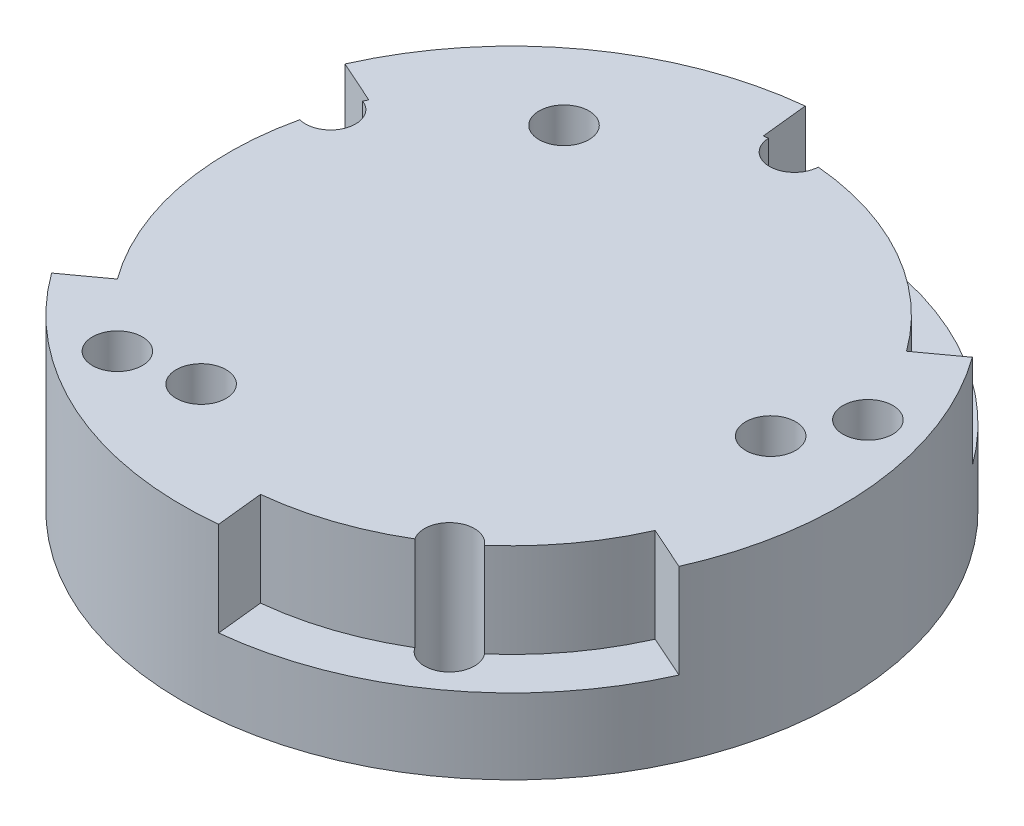
SolidWorks part; units mm, degrees
ref_plane "Front Plane" through (0, 0, 0) normal (0, 0, 1) x (1, 0, 0)
ref_plane "Top Plane" through (0, 0, 0) normal (0, 1, 0) x (1, 0, 0)
ref_plane "Right Plane" through (0, 0, 0) normal (1, 0, 0) x (0, 0, -1)
sketch "Sketch2" plane through (0, 0, 0) normal (0, 1, 0) x (1, 0, 0)
  circle A8 centre (0, 0) radius 35
  dimension "D1" = 70
extrude "Boss-Extrude1" add sketch "Sketch2" along normal blind 8
sketch "Sketch4" plane through (0, 8, 0) normal (0, 1, 0) x (1, 0, 0)
  circle A0 centre (0, 0) radius 30 construction
  circle A1 centre (0, 30) radius 2.65
  circle A2 centre (28.5317, 9.2705) radius 2.65
  circle A3 centre (17.6336, -24.2705) radius 2.65
  circle A4 centre (-17.6336, -24.2705) radius 2.65
  circle A5 centre (-28.5317, 9.2705) radius 2.65
  point P16 (0, 0)
  dimension "D1" = 5.3
  dimension "D2" = 30
  dimension "D4" = 30
  dimension "D5" = 30
  dimension "D3" = 5
extrude "Cut-Extrude1" cut sketch "Sketch4" against normal blind 8 from surface starting at face at (0, 8, 35)
sketch "Sketch5" plane through (0, 8, 0) normal (0, 1, 0) x (1, 0, 0)
  line L2 (0, 0) -> (-3.6585, 34.8083) construction
  line L3 (0, 0) -> (-31.9741, 14.2358) construction
  line L4 (-31.9741, 14.2358) -> (-27.4064, 12.2021)
  line L5 (0, 0) -> (-50000, 0) construction
  line L6 (28.3156, 20.5725) -> (24.2705, 17.6336)
  line L7 (-3.6585, 34.8083) -> (-3.1359, 29.8357)
  line L8 (31.9741, -14.2358) -> (27.4064, -12.2021)
  line L9 (3.6585, -34.8083) -> (3.1359, -29.8357)
  line L10 (-20.5725, 28.3156) -> (0, 0) construction
  line L11 (34.8083, 3.6585) -> (0, 0) construction
  line L12 (-14.2358, -31.9741) -> (0, 0) construction
  line L13 (-28.3156, -20.5725) -> (-24.2705, -17.6336)
  arc A2 (-3.6585, 34.8083) -> (-31.9741, 14.2358) centre (0, 0) ccw
  circle A3 centre (0, 0) radius 35 construction
  arc A4 (31.9741, -14.2358) -> (28.3156, 20.5725) centre (0, 0) ccw
  arc A5 (-28.3156, -20.5725) -> (3.6585, -34.8083) centre (0, 0) ccw
  circle A6 centre (0, 0) radius 25 construction
  circle A7 centre (-14.6946, 20.2254) radius 2.65
  circle A9 centre (24.863, 2.6132) radius 2.65
  circle A10 centre (0, 0) radius 30
  circle A11 centre (-10.1684, -22.8386) radius 2.65
  point P25 (0, 0)
  point P35 (0, 0)
  point P41 (0, 0)
  circle M1 centre (0, 30) radius 2.65
  circle M2 centre (28.5317, 9.2705) radius 2.65
  circle M3 centre (17.6336, -24.2705) radius 2.65
  circle M4 centre (-17.6336, -24.2705) radius 2.65
  circle M5 centre (-28.5317, 9.2705) radius 2.65
  circle M6 centre (0, 0) radius 35
  dimension "D1" = 60
  dimension "D2" = 3
  dimension "D3" = 50
  dimension "D4" = 5.3
  dimension "D8" = 60
  dimension "D6" = 24
  dimension "D5" = 3
extrude "Boss-Extrude2" add sketch "Sketch5" along normal blind 10 contours A10 L7 L4 M6 | A10 A11 A9 A7 M3 M2 M1 M5 M4 | A10 L8 L6 M6 M2 | A10 L13 L9 M6 M4 region at (-18.278, 8, -25.1575) region at (0, 8, 0) region at (-12.2497, 8, 28.6374) region at (31.0212, 8, -2.8007)
sketch "Sketch6" plane through (0, 18, 0) normal (0, 1, 0) x (1, 0, 0)
  circle A0 centre (0, 0) radius 25 construction
  circle A1 centre (-14.6946, 20.2254) radius 2.65
  circle A2 centre (24.863, 2.6132) radius 2.65
  circle A3 centre (-10.1684, -22.8386) radius 2.65
  point P14 (0, 0)
  dimension "D1" = 5.3
  dimension "D2" = 3
extrude "Cut-Extrude2" cut sketch "Sketch6" against normal up to surface (18 mm away) up to face at (0, 0, -27.35)
